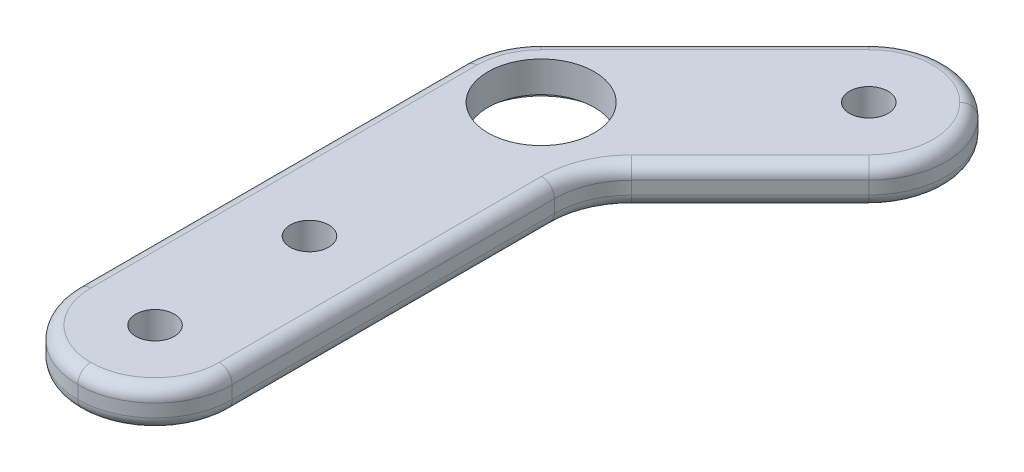
SolidWorks part; units mm, degrees
material "6061 Alloy"
ref_plane "Front Plane" through (0, 0, 0) normal (0, 0, 1) x (1, 0, 0)
ref_plane "Top Plane" through (0, 0, 0) normal (0, 1, 0) x (1, 0, 0)
ref_plane "Right Plane" through (0, 0, 0) normal (1, 0, 0) x (0, 0, -1)
sketch "Sketch1" plane through (0, 0, 0) normal (0, 1, 0) x (1, 0, 0)
  line L0 (0, 44.45) -> (0, -44.45) construction
  line L1 (-12.7, -44.45) -> (12.7, -44.45)
  line L2 (-12.7, -44.45) -> (-12.7, 31.75)
  line L3 (-12.7, 44.45) -> (12.7, 44.45) construction
  line L4 (12.7, -44.45) -> (12.7, 31.75)
  line L5 (-12.7, -44.45) -> (12.7, 44.45) construction
  line L6 (-12.7, 44.45) -> (12.7, -44.45) construction
  line L7 (0, 31.75) -> (35.921, 67.671) construction
  line L8 (8.9803, 22.7697) -> (44.9013, 58.6908)
  line L9 (44.9013, 58.6908) -> (26.9408, 76.6513)
  line L10 (26.9408, 76.6513) -> (-8.9803, 40.7303)
  line L11 (-8.9803, 40.7303) -> (8.9803, 22.7697) construction
  line L12 (12.7, 44.45) -> (12.7, 31.75) construction
  circle A0 centre (0, 31.75) radius 12.7
  circle A1 centre (0, -31.75) radius 3.175
  circle A2 centre (0, -6.35) radius 3.175
  circle A3 centre (0, 31.75) radius 8.7312
  circle A4 centre (26.9408, 58.6908) radius 3.175
  point P0 (0, 0)
  point P16 (35.921, 67.671)
  point P21 (0, 31.75)
  dimension "D4" = 12.7
  dimension "D1" = 6.35
  dimension "D7" = 38.1
  dimension "D8" = 12.7
  dimension "D9" = 17.4625
  dimension "D2" = 25.4
  dimension "D3" = 45
  dimension "D5" = 25.4
  dimension "D6" = 38.1
extrude "Boss-Extrude1" add sketch "Sketch1" along normal blind 6.35 contours A0 L2 L1 L4 L8 A2 A1 | A0 A3 | A0 L4 L8 L9 L10 A4 | A0 L8 L4 region at (-0.0256, 0, 11.0536) region at (-11.4014, 0, -36.4726) region at (11.9359, 0, -26.806) region at (21.2757, 0, -53.0842)
fillet "Fillet2" radius 12.7 5 edges at (12.7, 3.175, -26.4895) (26.9408, 3.175, -76.6513) (44.9013, 3.175, -58.6908) (-12.7, 3.175, 44.45) (12.7, 3.175, 44.45)
fillet "Fillet3" radius 2.1167 20 edges at (13.6667, 0, -26.0891) (12.7, 0, 5.2605) (8.9803, 0, 40.7303) (-8.9803, 0, 40.7303) (-12.7, 0, 0) (-11.7333, 0, -36.6101) (4.4901, 0, -54.2006) (26.9408, 0, -71.3908) (39.6408, 0, -58.6908) (13.6667, 6.35, -26.0891) (12.7, 6.35, 5.2605) (8.9803, 6.35, 40.7303) (-8.9803, 6.35, 40.7303) (-12.7, 6.35, 0) (-11.7333, 6.35, -36.6101) (4.4901, 6.35, -54.2006) (26.9408, 6.35, -71.3908) (39.6408, 6.35, -58.6908) (26.1704, 0, -39.9599) (26.1704, 6.35, -39.9599)
sketch "Sketch3" plane through (0, 0, 0) normal (0, -1, 0) x (1, 0, 0)
  circle A0 centre (0, -31.75) radius 10.2489
  dimension "D1" = 20.4978
extrude "Cut-Extrude1" cut sketch "Sketch3" against normal blind 1.27
